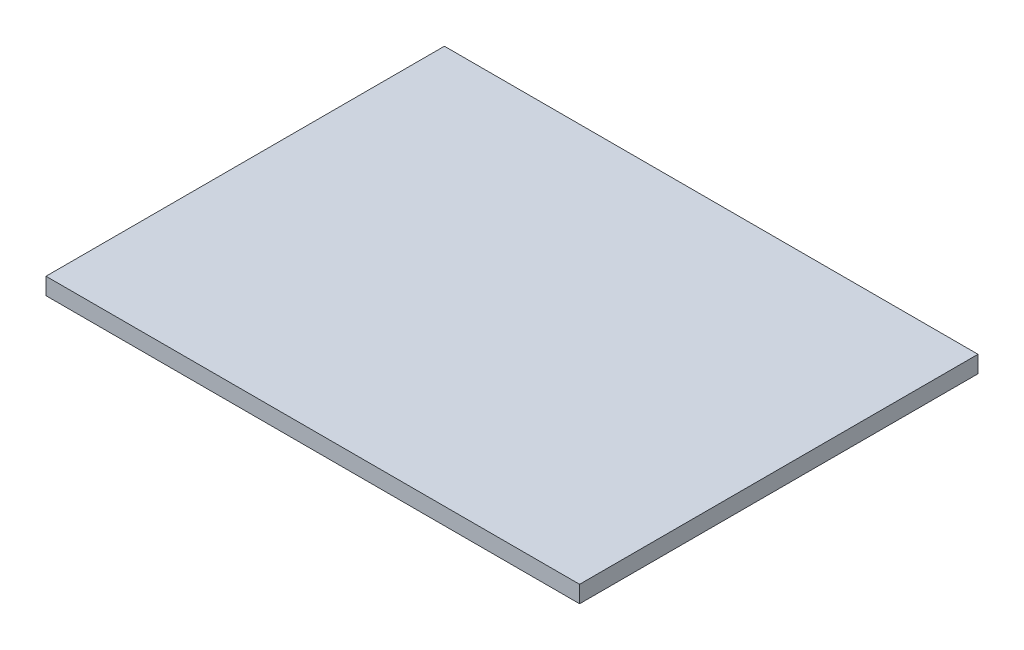
SolidWorks part; units mm, degrees
ref_plane "前视基准面" through (0, 0, 0) normal (0, 0, 1) x (1, 0, 0)
ref_plane "上视基准面" through (0, 0, 0) normal (0, 1, 0) x (1, 0, 0)
ref_plane "右视基准面" through (0, 0, 0) normal (1, 0, 0) x (0, 0, -1)
sketch "草图2" plane through (0, 0, 0) normal (0, 1, 0) x (1, 0, 0)
  line L1 (150, 112) -> (-150, 112)
  line L2 (150, 112) -> (150, -112)
  line L3 (150, -112) -> (-150, -112)
  line L4 (-150, 112) -> (-150, -112)
  line L5 (150, 112) -> (-150, -112) construction
  line L6 (150, -112) -> (-150, 112) construction
  point P0 (0, 0)
  dimension "D1" = 224
  dimension "D2" = 300
extrude "凸台-拉伸1" add sketch "草图2" along normal blind 9.5
sketch "草图3" plane through (0, 9.5, 0) normal (0, 1, 0) x (1, 0, 0)
  line L0 (-150, 0) -> (150, 0) construction
  line L1 (-150, 112) -> (-150, -112) construction
  line L2 (150, -112) -> (150, 112) construction
ref_plane "基准面1" through (0, 0, 0) normal (0, 0, -1) x (-1, 0, 0)
